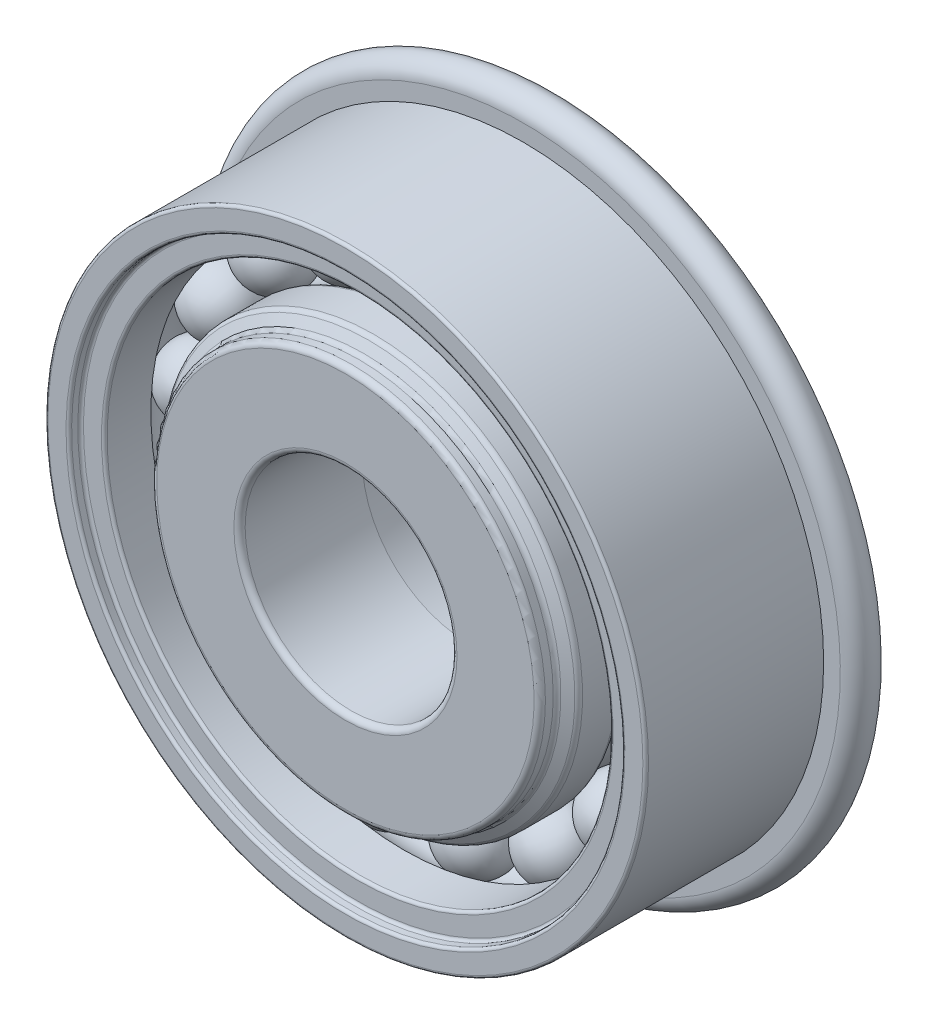
SolidWorks part; units mm, degrees
ref_plane "Front Plane" through (0, 0, 0) normal (0, 0, 1) x (1, 0, 0)
ref_plane "Top Plane" through (0, 0, 0) normal (0, 1, 0) x (1, 0, 0)
ref_plane "Right Plane" through (0, 0, 0) normal (1, 0, 0) x (0, 0, -1)
sketch "Sketch1" plane through (0, 0, 0) normal (1, 0, 0) x (0, 0, -1)
  line L0 (-5.5626, 0) -> (5.5626, 0) construction
  line L1 (3.9624, 0) -> (3.9624, 15.0114)
  line L2 (3.9624, 15.0114) -> (2.4384, 15.0114)
  line L3 (2.4384, 15.0114) -> (2.4384, 13.5001)
  line L4 (2.4384, 13.5001) -> (-5.5626, 13.5001)
  line L5 (-5.5626, 4.7625) -> (3.9624, 4.7625)
  line L6 (-5.5626, 8.7376) -> (5.5626, 8.7376)
  line L7 (-1.5621, 13.5001) -> (-1.5621, 10.3251) construction
  arc A0 (2.4384, 14.2494) -> (3.9624, 14.2494) centre (3.2004, 14.2494) cw
  point P4 (0, 0)
  dimension "Inner Ring Width" = 11.1252
  dimension "Flange OD" = 30.0228
  dimension "OD" = 27.0002
  dimension "Width" = 9.525
  dimension "ID" = 9.525
  dimension "Inner Ring OD" = 17.4752
  dimension "Flange Thickness" = 1.524
  dimension "Ball Diameter" = 3.175
  dimension "For Shaft Diameter" = 9.525
  dimension "For Housing ID" = 27.0002
sketch "Sketch2" plane through (0, 0, 0) normal (1, 0, 0) x (0, 0, -1)
  line L0 (2.4384, 13.5001) -> (-5.5626, 13.5001) construction
  line L1 (2.4384, 13.5001) -> (-5.5626, 13.5001)
  line L2 (2.4384, 13.5001) -> (2.4384, 14.2494)
  line L3 (3.9624, 14.2494) -> (3.9624, 11.3728)
  line L4 (3.9624, 0) -> (3.9624, 15.0114) construction
  line L5 (3.9624, 11.3728) -> (-0.1873, 11.3728)
  line L6 (-5.0308, 11.3728) -> (-5.0308, 12.4365)
  line L7 (-5.0308, 12.4365) -> (-5.5626, 12.4365)
  line L8 (-5.5626, 12.4365) -> (-5.5626, 13.5001)
  line L9 (-1.5621, 12.1666) -> (-1.5621, 13.5001) construction
  line L10 (-1.5621, 4.7625) -> (-1.5621, 6.7501) construction
  line L11 (-1.5621, 6.7501) -> (-1.5621, 8.7376) construction
  line L12 (-5.5626, 8.7376) -> (5.5626, 8.7376) construction
  line L13 (-5.5626, 4.7625) -> (3.9624, 4.7625) construction
  line L14 (-1.5621, 12.1666) -> (-1.5621, 11.3728) construction
  line L15 (-1.5621, 11.3728) -> (-1.5621, 10.5791) construction
  line L16 (-2.9369, 11.3728) -> (-5.0308, 11.3728)
  line L17 (-4.499, 12.4365) -> (-5.5626, 12.4365) construction
  arc A0 (3.9624, 14.2494) -> (2.4384, 14.2494) centre (3.2004, 14.2494) ccw construction
  arc A1 (3.9624, 14.2494) -> (2.4384, 14.2494) centre (3.2004, 14.2494) ccw
  circle A2 centre (-1.5621, 10.5791) radius 1.5875 construction
  arc A3 (-2.9369, 11.3728) -> (-0.1873, 11.3728) centre (-1.5621, 10.5791) cw
  point P10 (-1.5621, 13.5001)
  point P12 (-1.5621, 8.9916)
  point P23 (-1.5621, 8.7376)
  point P24 (-1.5621, 11.3728)
  point P33 (-5.0308, 12.4365)
  dimension "D1" = 3.175
  dimension "D2" = 0.254
revolve "Revolve1" add sketch "Sketch2" angle 360 about L0
sketch "Sketch3" plane through (0, 0, 0) normal (1, 0, 0) x (0, 0, -1)
  line L0 (-5.5626, 8.7376) -> (5.5626, 8.7376) construction
  line L1 (-5.5626, 8.7376) -> (-4.811, 8.7376)
  line L2 (5.5626, 8.7376) -> (5.5626, 4.7625)
  line L3 (5.5626, 4.7625) -> (-5.5626, 4.7625)
  line L4 (-5.5626, 4.7625) -> (-5.5626, 8.7376)
  line L5 (2.4384, 8.7376) -> (5.5626, 8.7376)
  line L6 (-4.811, 8.7376) -> (-4.4353, 9.3885)
  line L7 (-4.4353, 9.3885) -> (-2.6121, 9.3885)
  line L8 (-0.5121, 9.3885) -> (2.0626, 9.3885)
  line L9 (2.0626, 9.3885) -> (2.4384, 8.7376)
  line L10 (-1.5621, 10.5791) -> (-1.5621, 9.7854) construction
  line L11 (-1.5621, 9.7854) -> (-1.5621, 8.9916) construction
  circle A2 centre (-1.5621, 10.5791) radius 1.5875 construction
  arc A3 (-2.6121, 9.3885) -> (-0.5121, 9.3885) centre (-1.5621, 10.5791) ccw
  point P12 (-1.5621, 9.3885)
  dimension "D1" = 60
  dimension "D2" = 60
revolve "Revolve2" add sketch "Sketch3" angle 360 about L0
sketch "Sketch5" plane through (0, 0, 0) normal (1, 0, 0) x (0, 0, -1)
  line L0 (5.5626, 5.7563) -> (5.5626, 4.7625)
  line L2 (4.893, 5.1944) -> (-0.0436, 4.7625)
  line L8 (5.3173, 5.822) -> (5.5626, 5.7563) construction
  line L12 (5.5626, 8.7376) -> (5.5626, 4.7625) construction
  line L13 (5.5626, 5.7563) -> (5.5626, 6.7501) construction
  line L14 (5.5626, 4.7625) -> (-5.5626, 4.7625) construction
  line L15 (-0.0436, 4.7625) -> (5.5626, 4.7625)
  arc A0 (5.5626, 5.7563) -> (4.893, 5.1944) centre (4.8266, 5.9535) cw
  dimension "D3" = 0.762
  dimension "D1" = 105
  dimension "D2" = 0.254
  dimension "D4" = 5
revolve "Cut-Revolve2" cut sketch "Sketch5" angle 360 about L0
sketch "Sketch6" plane through (0, 0, 0) normal (1, 0, 0) x (0, 0, -1)
  line L0 (5.3173, 5.822) -> (5.5626, 5.7563) construction
  line L1 (5.3173, 5.822) -> (5.5626, 5.7563)
  line L2 (5.3173, 5.822) -> (5.5626, 6.7377) construction
  line L3 (5.5626, 8.7376) -> (5.5626, 4.7625) construction
  line L4 (5.5626, 6.7377) -> (5.5626, 5.7563) construction
  line L5 (4.8708, 5.4474) -> (3.9624, 5.368)
  line L6 (3.9624, 0) -> (3.9624, 15.0114) construction
  line L7 (4.893, 5.1944) -> (-0.0436, 4.7625) construction
  line L8 (3.9624, 5.368) -> (3.9624, 5.4954)
  line L9 (5.1946, 5.8549) -> (5.5626, 5.8549)
  line L10 (4.8598, 5.5739) -> (3.9624, 5.4954)
  line L11 (5.5626, 5.8549) -> (5.5626, 5.7563)
  arc A1 (5.3173, 5.822) -> (4.8708, 5.4474) centre (4.8266, 5.9535) cw
  arc A2 (4.8598, 5.5739) -> (5.1946, 5.8549) centre (4.8266, 5.9535) ccw
  arc A3 (4.893, 5.1944) -> (5.5626, 5.7563) centre (4.8266, 5.9535) ccw construction
  dimension "D1" = 0.127
revolve "Cut-Revolve3" cut sketch "Sketch6" angle 360 about L0
fillet "Fillet4" radius 0.762 1 edges at (0, -5.8549, -5.5626)
sketch "Sketch7" plane through (0, 0, 0) normal (1, 0, 0) x (0, 0, -1)
  line L0 (5.5626, 6.7501) -> (5.5626, 7.7438) construction
  line L1 (5.5626, 8.7376) -> (5.5626, 4.7625) construction
  line L2 (5.5626, 7.7438) -> (5.5626, 8.7376) construction
  line L3 (5.5626, 7.7438) -> (5.5626, 8.7376)
  line L4 (5.5626, 8.7376) -> (5.2313, 8.7376)
  line L5 (-5.5626, 8.7376) -> (5.5626, 8.7376) construction
  line L6 (5.2313, 8.7376) -> (5.2313, 8.4063)
  line L7 (5.2313, 8.4063) -> (5.2313, 8.0751)
  line L8 (5.2313, 8.0751) -> (5.2313, 7.7438)
  line L9 (5.2313, 7.7438) -> (5.5626, 7.7438)
revolve "Cut-Revolve4" cut sketch "Sketch7" angle 360 about L0
sketch "Sketch11" plane through (0, 0, 0) normal (1, 0, 0) x (0, 0, -1)
  line L0 (-1.5621, 12.1666) -> (-1.5621, 8.9916)
  circle A0 centre (-1.5621, 10.5791) radius 1.5875 construction
  arc A1 (-1.5621, 8.9916) -> (-1.5621, 12.1666) centre (-1.5621, 10.5791) ccw
revolve "Revolve3" add sketch "Sketch11" angle 360 about L0
pattern_circular "CirPattern3" count 17 over 360 about axis through (0, 0, 5.5626) along (0, 0, -1) of bodies 111
fillet "Fillet2" radius 0.127 2 edges at (0, -12.4365, 5.0308) (0, -11.3728, 5.0308)
fillet "Fillet3" radius 0.127 2 edges at (0, -13.5001, 5.5626) (0, -12.4365, 5.5626)
fillet "Fillet5" radius 0.254 9 edges at (0, -8.7376, -5.2313) (0, -8.7376, -2.4384) (0, -9.3885, 0.5121) (0, -9.3885, 2.6121) (0, -9.3885, 4.4353) (0, -8.7376, 4.811) (0, -8.7376, 5.5626) (0, -4.7625, 5.5626) (0, -7.7438, -5.5626)
sketch "Sketch12" plane through (0, 0, -3.9624) normal (0, 0, -1) x (-1, 0, 0)
  line L0 (0, 11.3728) -> (0, 14.2494) construction
  circle A0 centre (0, 0) radius 11.3728 construction
  circle A1 centre (0, 0) radius 11.3728
  circle A2 centre (0, 0) radius 14.2494 construction
  circle A3 centre (0, 0) radius 12.8111
  point P8 (0, 12.8111)
extrude "Cut-Extrude1" cut sketch "Sketch12" against normal blind 1.143
sketch "Sketch13" plane through (0, 0, 0) normal (0, 0, 1) x (1, 0, 0)
  circle A0 centre (0, 0) radius 8.7376
  circle A1 centre (0, 0) radius 15.0114
  circle A2 centre (0, 0) radius 13.5001
  circle A3 centre (0, 0) radius 4.7625
  point P0 (0, 8.7376)
  point P5 (0, 15.0114)
  point P8 (0, 13.5001)
  point P11 (0, 4.7625)
equation "\"D1@Sketch2\"=\"Ball Diameter@Sketch1\""
equation "\"D1@Cut-Extrude1\"=\"Flange Thickness@Sketch1\"*.75"
